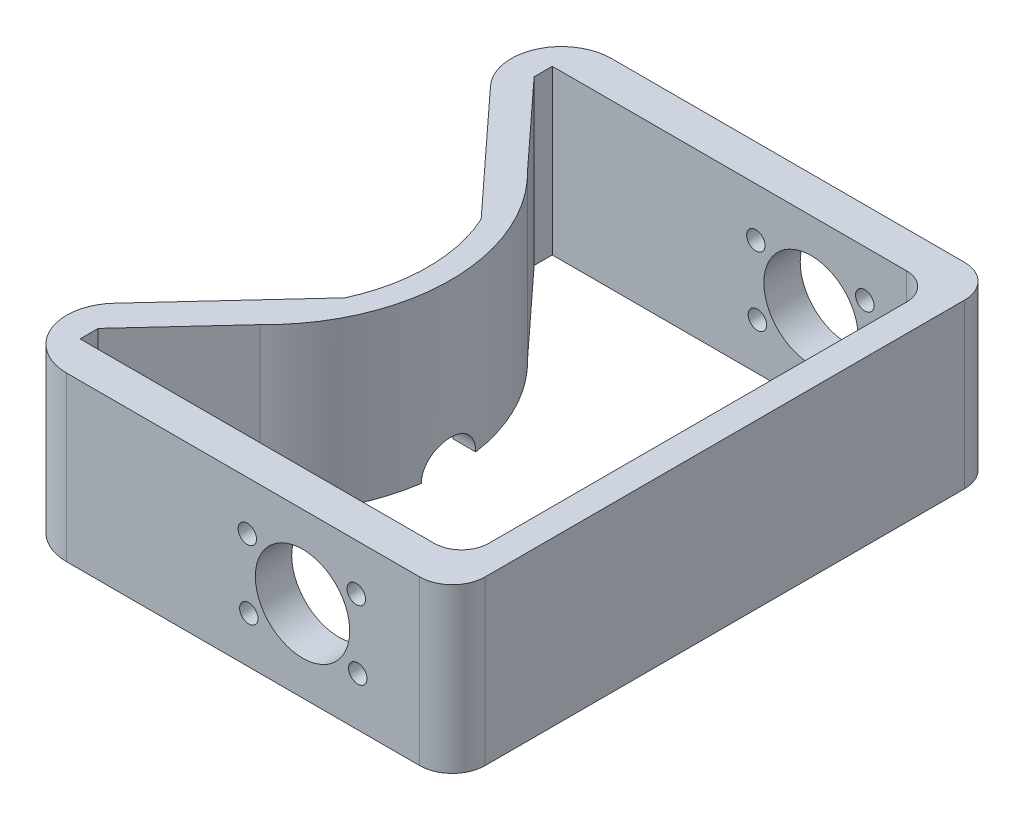
SolidWorks part; units mm, degrees
material "TPU"
ref_plane "Front Plane" through (0, 0, 0) normal (0, 0, 1) x (1, 0, 0)
ref_plane "Top Plane" through (0, 0, 0) normal (0, 1, 0) x (1, 0, 0)
ref_plane "Right Plane" through (0, 0, 0) normal (1, 0, 0) x (0, 0, -1)
sketch "Sketch1" plane through (0, 0, 0) normal (0, 1, 0) x (1, 0, 0)
  line L0 (66.675, 17.145) -> (66.675, 128.905) construction
  line L1 (-28.575, 9.525) -> (66.675, 9.525)
  line L2 (-28.575, 9.525) -> (-28.575, 17.9917)
  line L3 (-28.575, 17.9917) -> (66.675, 17.9917)
  line L4 (66.675, 9.525) -> (66.675, 17.9917)
  line L5 (-28.575, 9.525) -> (66.675, 17.9917) construction
  line L6 (-28.575, 17.9917) -> (66.675, 9.525) construction
  line L9 (-28.575, 9.525) -> (59.055, 9.525) construction
  point P0 (19.05, 13.7583)
  point P5 (0, 0)
  point P15 (19.05, 9.525)
  dimension "D1" = 95.25
  dimension "D2" = 8.4667
extrude "Boss-Extrude1" add sketch "Sketch1" along normal blind 38.1
sketch "Sketch2" plane through (0, 38.1, 0) normal (0, 1, 0) x (1, 0, 0)
  line L1 (60.325, 9.525) -> (66.675, 9.525)
  line L2 (60.325, 9.525) -> (60.325, 136.525)
  line L3 (60.325, 136.525) -> (66.675, 136.525)
  line L4 (66.675, 9.525) -> (66.675, 136.525)
  line L6 (32.8756, 15.875) -> (32.8756, 130.175) construction
  line L7 (-20.4, 15.875) -> (58.5, 15.875) construction
  line L8 (58.5, 130.175) -> (-20.4, 130.175) construction
  dimension "D1" = 127
  dimension "D2" = 6.35
extrude "Boss-Extrude2" add sketch "Sketch2" against normal up to surface (38.1 mm away) up to face at (19.05, 0, -13.7583)
sketch "Sketch3" plane through (0, 38.1, 0) normal (0, 1, 0) x (1, 0, 0)
  line L0 (-28.575, 17.9917) -> (-28.575, 9.525) construction
  line L1 (60.325, 136.525) -> (-28.575, 136.525)
  line L2 (60.325, 136.525) -> (60.325, 128.0583)
  line L3 (60.325, 128.0583) -> (-28.575, 128.0583)
  line L4 (-28.575, 136.525) -> (-28.575, 128.0583)
extrude "Boss-Extrude3" add sketch "Sketch3" against normal up to surface (38.1 mm away) up to face at (32.8083, 0, -54.6806)
sketch "Sketch4" plane through (0, 0, -136.525) normal (0, 0, -1) x (-1, 0, 0)
  line L0 (3.175, 38.1) -> (-66.675, 38.1) construction
  line L1 (-66.675, 19.05) -> (3.175, 19.05) construction
  line L2 (-66.675, 0) -> (-66.675, 38.1) construction
  line L5 (28.575, 19.05) -> (3.175, 19.05) construction
  line L6 (28.575, 0) -> (28.575, 38.1) construction
  circle A0 centre (-31.75, 19.05) radius 11
  point P7 (-31.75, 38.1)
  dimension "D1" = 22
  dimension "D2" = 25.4
extrude "Cut-Extrude1" cut sketch "Sketch4" against normal through all contours A0 region at (31.75, 19.05, -136.525)
sketch "Sketch5" plane through (0, 0, -136.525) normal (0, 0, -1) x (-1, 0, 0)
  circle A0 centre (-18.8777, 26.7049) radius 2.1527
  circle A1 centre (-19.2285, 10.8337) radius 2.1527
  circle A2 centre (-44.6223, 11.3951) radius 2.1527
  circle A3 centre (-44.2715, 27.2663) radius 2.1526
  circle A4 centre (-44.6223, 11.3951) radius 2.1527 construction
  circle A5 centre (-18.8777, 26.7049) radius 2.1526 construction
  circle A6 centre (-19.2285, 10.8337) radius 2.1527 construction
  circle A9 centre (-44.2715, 27.2663) radius 2.1526 construction
extrude "Cut-Extrude2" cut sketch "Sketch5" against normal through all
fillet "Fillet1" radius 7.62 2 edges at (66.675, 19.05, -9.525) (66.675, 19.05, -136.525)
sketch "Sketch10" plane through (0, 38.1, 0) normal (0, 1, 0) x (1, 0, 0)
  line L0 (-28.575, 9.525) -> (59.055, 9.525) construction
  line L2 (-28.575, 17.9917) -> (-28.575, 9.525)
  line L5 (66.675, 73.025) -> (-147.9374, 73.025) construction
  line L7 (-28.575, 136.525) -> (-34.925, 136.525)
  line L11 (-34.925, 25.781) -> (-5.996, 57.15)
  line L15 (-28.575, 17.9917) -> (-28.575, 22.225)
  line L16 (-28.575, 22.225) -> (-10.4944, 41.8306)
  line L17 (-28.575, 123.825) -> (-10.4944, 104.2194)
  line L18 (-34.925, 120.269) -> (-5.996, 88.9)
  line L19 (-10.4944, 41.8306) -> (-5.996, 57.15) construction
  line L22 (-28.575, 136.525) -> (-28.575, 123.825)
  line L26 (-34.925, 136.525) -> (-34.925, 120.269)
  line L27 (-34.925, 25.781) -> (-34.925, 9.525)
  line L28 (-34.925, 9.525) -> (-28.575, 9.525)
  line L29 (66.675, 17.145) -> (66.675, 128.905) construction
  arc A0 (-5.996, 57.15) -> (-5.996, 88.9) centre (-40.6312, 73.025) ccw
  arc A2 (-10.4944, 104.2194) -> (-10.4944, 41.8306) centre (-40.6312, 73.025) cw
  point P3 (0, 0)
  point P10 (0, 0)
  point P13 (-11.0673, 73.025)
  point P14 (0, 0)
  point P25 (0, 0)
  dimension "D7" = 31.75
  dimension "D6" = 38.1
  dimension "D1" = 16.256
  dimension "D2" = 6.35
  dimension "D3" = 12.7
  dimension "D4" = 42.672
  dimension "D5" = 26.67
extrude "Boss-Extrude4" add sketch "Sketch10" against normal up to surface (38.1 mm away) up to face at (26.0966, 0, -73.025)
sketch "Sketch12" plane through (60.325, 0, 0) normal (-1, 0, 0) x (0, 0, 1)
  line L0 (-88.9, 0) -> (-79.375, 0) construction
  line L1 (-88.9, 0) -> (-57.15, 0) construction
  line L2 (-57.15, 0) -> (-66.675, 0) construction
  line L3 (-79.375, 0) -> (-66.675, 0)
  arc A0 (-79.375, 0) -> (-66.675, 0) centre (-73.025, 0) cw
  point P9 (0, 0)
  dimension "D1" = 12.7
extrude "Cut-Extrude8" cut sketch "Sketch12" along normal up to surface (95.25 mm away) up to face at (-34.925, 19.05, -128.397)
fillet "Fillet2" 2 edges at (-34.925, 19.05, -120.269) (-34.925, 19.05, -136.525) type full round first side face at (-20.4605, 19.05, -104.5845) second side face at (42.1188, 27.2663, -136.525) middle face at (-34.925, 19.05, -128.397)
sketch "Sketch13" plane through (0, 0, 0) normal (0, -1, 0) x (-1, 0, 0)
  line L0 (-82.55, 73.025) -> (49917.45, 73.025) construction
  line L1 (-66.675, 17.145) -> (-66.675, 128.905) construction
  point P4 (-66.675, 73.025)
fillet "Fillet3" 2 edges at (-34.925, 19.05, -25.781) (-34.925, 19.05, -9.525) type full round first side face at (-20.4605, 19.05, -41.4655) second side face at (42.1188, 27.2663, -9.525) middle face at (-34.925, 19.05, -17.653)
fillet "Fillet4" radius 6.35 2 edges at (60.325, 19.05, -128.0583) (60.325, 19.05, -17.9917)
